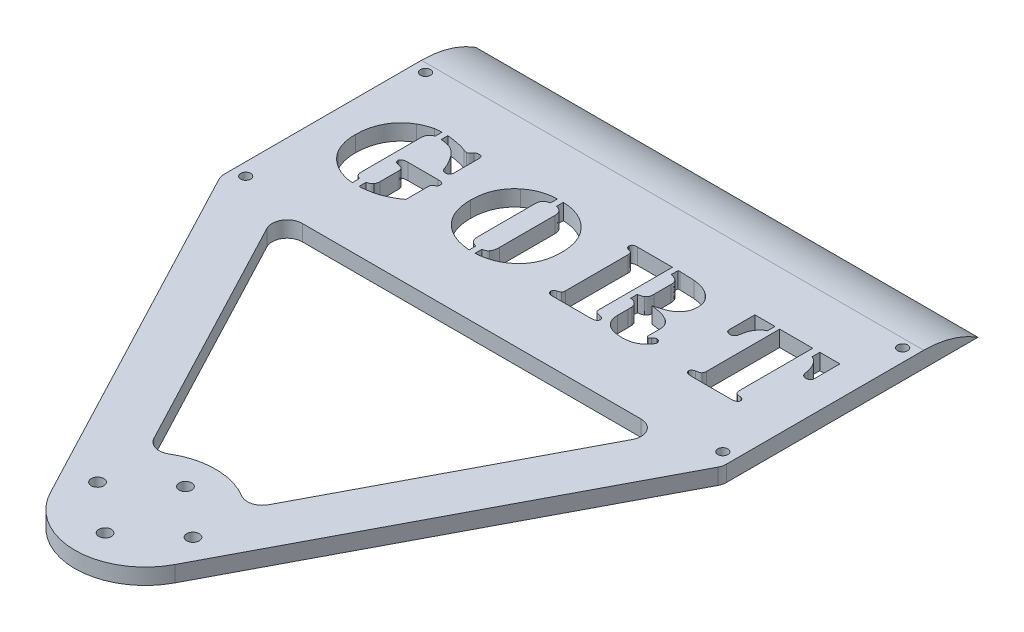
SolidWorks part; units mm, degrees
material "6061 Alloy"
ref_plane "Front Plane" through (0, 0, 0) normal (0, 0, 1) x (1, 0, 0)
ref_plane "Top Plane" through (0, 0, 0) normal (0, 1, 0) x (1, 0, 0)
ref_plane "Right Plane" through (0, 0, 0) normal (1, 0, 0) x (0, 0, -1)
sketch "Sketch1" plane through (0, 0, 0) normal (0, 1, 0) x (1, 0, 0)
  line L0 (0, 25.405) -> (0, -86.8356) construction
  line L2 (50, -25.405) -> (50, 25.405)
  line L3 (50, 25.405) -> (-50, 25.405)
  line L4 (-50, -25.405) -> (-50, 25.405)
  line L5 (50, -25.405) -> (-50, 25.405) construction
  line L6 (50, 25.405) -> (-50, -25.405) construction
  line L7 (-50, -25.405) -> (-12.3911, -96.9212)
  line L8 (50, -25.405) -> (12.3911, -96.9212)
  line L9 (-38.7016, -25.405) -> (-9.7849, -80.3922)
  line L10 (38.7016, -25.405) -> (9.7849, -80.3922)
  line L11 (-38.7016, -25.405) -> (38.7016, -25.405)
  line L12 (-50, -25.405) -> (50, -25.405) construction
  circle A0 centre (0, -90.405) radius 14 construction
  arc A1 (-12.3911, -96.9212) -> (12.3911, -96.9212) centre (0, -90.405) ccw
  arc A2 (-9.7849, -80.3922) -> (9.7849, -80.3922) centre (0, -90.405) cw
  point P0 (0, 0)
  dimension "D3" = 28
  dimension "D1" = 100
  dimension "D2" = 50.81
  dimension "D4" = 65
  dimension "D5" = 10
extrude "Boss-Extrude1" add sketch "Sketch1" along normal blind 3.175
fillet "Fillet1" radius 3 4 edges at (-9.7849, 1.5875, 80.3922) (9.7849, 1.5875, 80.3922) (38.7016, 1.5875, 25.405) (-38.7016, 1.5875, 25.405)
fillet "Fillet2" radius 3 2 edges at (-50, 1.5875, 25.405) (50, 1.5875, 25.405)
sketch "Sketch2" plane through (0, 3.175, 0) normal (0, 1, 0) x (1, 0, 0)
  line L2 (-50, 25.405) -> (-50, -24.6643) construction
  line L3 (50, 25.405) -> (-50, 25.405) construction
  circle A0 centre (0, -82.405) radius 1.25
  circle A1 centre (0, -98.405) radius 1.25
  circle A2 centre (-9.5, -90.405) radius 1.25
  circle A3 centre (9.5, -90.405) radius 1.25
  point P0 (0, -90.405)
  point P13 (0, -90.405)
  point P17 (0, -90.405)
  dimension "D1" = 2.5
  dimension "D3" = 2
  dimension "D2" = 8
  dimension "D5" = 9.5
  dimension "D6" = 2
extrude "Cut-Extrude1" cut sketch "Sketch2" against normal blind 8.5704
sketch "Sketch3" plane through (0, 3.175, 0) normal (0, 1, 0) x (1, 0, 0)
  line L0 (50, -24.6643) -> (50, 25.405) construction
  line L1 (50, 25.405) -> (-50, 25.405) construction
  line L2 (50, 0.3704) -> (-50, 0.3704) construction
  line L3 (-50, 25.405) -> (-50, -24.6643) construction
  line L4 (0, 25.405) -> (0, -25.405) construction
  line L5 (33.7344, -25.405) -> (-33.7344, -25.405) construction
  circle A0 centre (47.5, 12.905) radius 1
  circle A4 centre (47.5, -22.905) radius 1
  circle A5 centre (-47.5, -22.905) radius 1
  circle A6 centre (-47.5, 12.905) radius 1
  dimension "D1" = 2
  dimension "D4" = 2.5
  dimension "D2" = 2.5
  dimension "D3" = 12.5
  dimension "D5" = 2.5
extrude "Cut-Extrude2" cut sketch "Sketch3" against normal through all
fillet "Fillet4" radius 20 1 edges at (0, 3.175, -25.405)
sketch "Sketch4" plane through (0, 3.175, 0) normal (0, 1, 0) x (1, 0, 0)
  line L0 (-50, -5.0361) -> (50, -5.0361) construction
  line L1 (-50, 14.5921) -> (-50, -24.6643) construction
  line L2 (50, -24.6643) -> (50, 14.5921) construction
  line L3 (0, -25.405) -> (0, 14.5921) construction
  line L4 (33.7344, -25.405) -> (-33.7344, -25.405) construction
  line L5 (50, 14.5921) -> (-50, 14.5921) construction
  line L6 (-50, -13.0361) -> (50, -13.0361) construction
  text T0 "GORT" font "Stencil" height in points 72
  dimension "D1" = 8
extrude "Cut-Extrude3" cut sketch "Sketch4" against normal up to surface (3.175 mm away) up to face at (-47.5, 0, -13.905)
